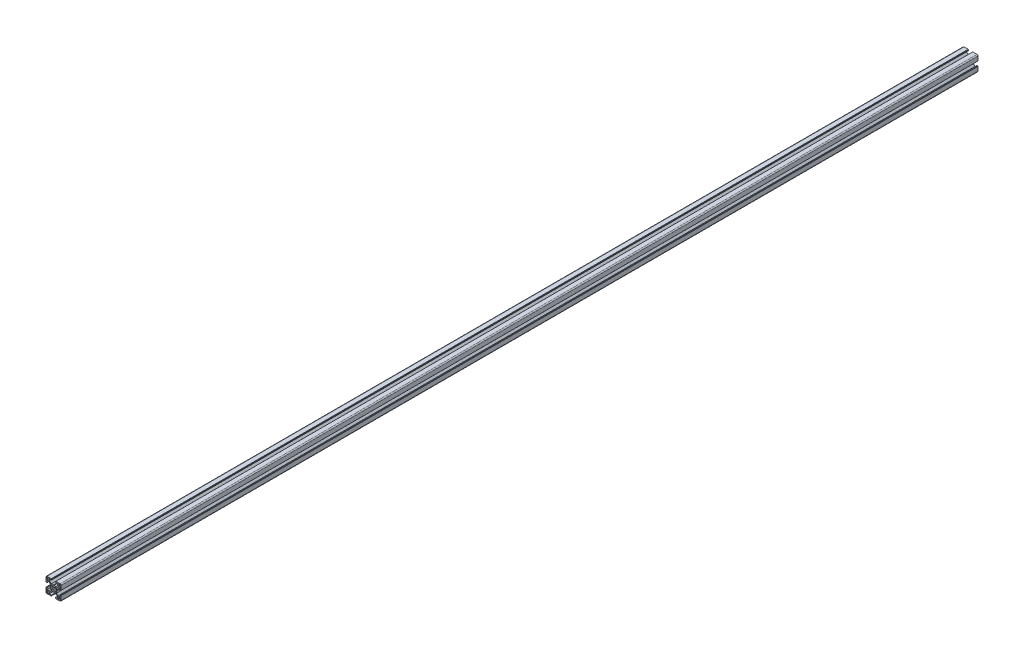
SolidWorks part; units mm, degrees
material "6061-T6 (SS)"
ref_plane "Front Plane" through (0, 0, 0) normal (0, 0, 1) x (1, 0, 0)
ref_plane "Top Plane" through (0, 0, 0) normal (0, 1, 0) x (1, 0, 0)
ref_plane "Right Plane" through (0, 0, 0) normal (1, 0, 0) x (0, 0, -1)
sketch "Sketch2" plane through (0, 0, 0) normal (0, 0, 1) x (1, 0, 0)
  line L0 (0, 15) -> (0, -15) construction
  line L1 (-15, 0) -> (15, 0) construction
  line L2 (4, -15) -> (15, -15)
  line L3 (15, -15) -> (15, -4)
  line L4 (4, -15) -> (4, -12.885)
  line L6 (8.25, -9.7455) -> (4.5045, -6)
  line L7 (0, 0) -> (15, -15) construction
  line L8 (15, -4) -> (12.885, -4)
  line L11 (4.55, -15) -> (4.55, -14.45) construction
  line L12 (4, -12.885) -> (8.25, -12.885)
  line L13 (8.25, -12.885) -> (8.25, -9.7455)
  line L14 (4.55, -14.45) -> (4, -14.45) construction
  line L15 (14.45, -4) -> (14.45, -4.55) construction
  line L16 (14.45, -4.55) -> (15, -4.55) construction
  line L17 (12.885, -4) -> (12.885, -8.25)
  line L18 (12.885, -8.25) -> (9.7455, -8.25)
  line L19 (9.7455, -8.25) -> (6, -4.5045)
  line L20 (7.8728, -6.3772) -> (6.3772, -7.8728) construction
  line L21 (11.625, -13.875) -> (11.625, -15) construction
  line L22 (9.375, -13.875) -> (13.875, -13.875)
  line L23 (9.375, -13.875) -> (9.375, -9.375)
  line L24 (9.375, -9.375) -> (13.875, -9.375)
  line L25 (13.875, -13.875) -> (13.875, -9.375)
  line L26 (11.625, -9.375) -> (11.625, -13.875) construction
  line L27 (9.375, -11.625) -> (13.875, -11.625) construction
  line L28 (13.875, -11.625) -> (15, -11.625) construction
  line L29 (8.25, -12.885) -> (9.375, -12.885) construction
  line L30 (4.5045, -6) -> (0.6555, -6)
  line L31 (0.6555, -6) -> (0, -5.45)
  line L32 (0, -6) -> (0, -5.45) construction
  circle A0 centre (0, 0) radius 3.5
  arc A2 (9.375, -12.885) -> (10.365, -13.875) centre (10.365, -12.885) ccw construction
  point P8 (0, -6)
  point P15 (4.55, -15)
  point P16 (7.125, -7.125)
  point P33 (11.625, -11.625)
  dimension "Center Hole Diameter" = 7
  dimension "Rail Height" = 30
  dimension "Rail Width" = 30
  dimension "T-Slot Width" = 8
  dimension "Slot Depth" = 9
  dimension "Slot Inner Width" = 16.5
  dimension "Step Width" = 9.1
  dimension "D1" = 1.125
  dimension "D2" = 2.115
  dimension "D3" = 50
sketch "Sketch3" plane through (0, 0, 0) normal (1, 0, 0) x (0, 0, -1)
  line L0 (-76.2, -15) -> (76.2, -15) construction
  line L1 (-50.8, 0) -> (50.8, 0) construction
  dimension "D1" = 25.4
  dimension "Length" = 152.4
sketch "Sketch4" plane through (0, 0, 0) normal (0, 0, 1) x (1, 0, 0)
  line L22 (0, -5.45) -> (0.6555, -6)
  line L23 (0.6555, -6) -> (4.5045, -6)
  line L24 (4.5045, -6) -> (8.25, -9.7455)
  line L25 (8.25, -9.7455) -> (8.25, -12.885)
  line L26 (8.25, -12.885) -> (4, -12.885)
  line L27 (4, -12.885) -> (4, -14.45)
  line L28 (4, -14.45) -> (4.55, -14.45)
  line L29 (4.55, -14.45) -> (4.55, -15)
  line L30 (4.55, -15) -> (12.885, -15)
  line L31 (4, -15) -> (15, -15) construction
  line L32 (15, -15) -> (15, -4) construction
  line L33 (15, -12.885) -> (15, -4.55)
  line L34 (15, -4.55) -> (14.45, -4.55)
  line L35 (14.45, -4.55) -> (14.45, -4)
  line L36 (14.45, -4) -> (12.885, -4)
  line L37 (12.885, -4) -> (12.885, -8.25)
  line L38 (12.885, -8.25) -> (9.7455, -8.25)
  line L39 (9.7455, -8.25) -> (6, -4.5045)
  line L40 (6, -4.5045) -> (6, -0.6555)
  line L41 (6, -0.6555) -> (5.45, 0)
  line L42 (-15, 0) -> (15, 0) construction
  line L43 (0, -5.45) -> (0, -3.5)
  line L44 (0, 15) -> (0, -15) construction
  line L45 (3.5, 0) -> (5.45, 0)
  line L46 (1.8108, -2.9952) -> (3.4913, -4.6757)
  line L47 (3.4913, -4.6757) -> (4.6757, -3.4913)
  line L48 (4.6757, -3.4913) -> (2.9952, -1.8108)
  line L49 (0, 0) -> (15, -15) construction
  line L50 (9.375, -13.875) -> (13.875, -13.875) construction
  line L51 (13.875, -13.875) -> (13.875, -9.375) construction
  line L52 (9.375, -13.875) -> (9.375, -9.375) construction
  line L53 (9.375, -9.375) -> (13.875, -9.375) construction
  line L54 (9.375, -10.365) -> (9.375, -12.885)
  line L55 (10.365, -13.875) -> (12.885, -13.875)
  line L56 (13.875, -12.885) -> (13.875, -10.365)
  line L57 (10.365, -9.375) -> (12.885, -9.375)
  arc A12 (12.885, -15) -> (15, -12.885) centre (12.885, -12.885) ccw
  circle A13 centre (0, 0) radius 3.5 construction
  arc A14 (0, -3.5) -> (1.8108, -2.9952) centre (0, 0) ccw
  arc A15 (3.5, 0) -> (2.9952, -1.8108) centre (0, 0) cw
  circle A16 centre (0, 0) radius 5.775 construction
  arc A17 (9.375, -12.885) -> (10.365, -13.875) centre (10.365, -12.885) ccw
  arc A18 (9.375, -12.885) -> (10.365, -13.875) centre (10.365, -12.885) ccw construction
  arc A19 (12.885, -13.875) -> (13.875, -12.885) centre (12.885, -12.885) ccw
  arc A20 (9.375, -10.365) -> (10.365, -9.375) centre (10.365, -10.365) cw
  arc A21 (12.885, -9.375) -> (13.875, -10.365) centre (12.885, -10.365) cw
  point P40 (4.0835, -4.0835)
  dimension "D1" = 11.55
  dimension "D2" = 0.22
extrude "Boss-Extrude1" add sketch "Sketch4" along normal blind 1828.8
mirror "Mirror1" about plane through (0, 0, 0) normal (1, 0, 0) of bodies 134
mirror "Mirror2" about plane through (0, 0, 0) normal (0, 1, 0) of bodies 135
sketch "Sketch5" plane through (0, 0, 1828.8) normal (0, 0, 1) x (1, 0, 0)
  line L0 (-5.675, 12.885) -> (-5.4, 13.16)
  line L1 (-8.25, 12.885) -> (-4, 12.885) construction
  line L2 (-5.4, 13.16) -> (-5.125, 12.885)
  line L3 (0, 15) -> (0, -15) construction
  line L4 (-5.675, 12.885) -> (-5.125, 12.885)
  dimension "D1" = 0.275
  dimension "D2" = 5.4
extrude "Cut-Extrude1" cut sketch "Sketch5" against normal through all both and the other way through all
equation "\"D1@Boss-Extrude1\"= \"table_length\""
equation "\"D1@Sketch2\"=\"Slot Depth@Sketch2\"*0.125"
equation "\"D2@Sketch2\"=\"Slot Depth@Sketch2\"*0.235"
equation "\"D1@Sketch4\"=\"Center Hole Diameter@Sketch2\"*1.65"
equation "\"D2@Sketch4\"=(\"Step Width@Sketch2\"-\"T-Slot Width@Sketch2\")*0.2"
equation "\"D1@Sketch5\"=(\"Step Width@Sketch2\"-\"T-Slot Width@Sketch2\")*0.5*0.5"
equation "\"D2@Sketch5\"=\"T-Slot Width@Sketch2\"*1.35*0.5"
equation "\"altitude_horizontal_rail_length\"=10in"
equation "\"altitude_vertictal_rail_length\"=12in"
equation "\"table_length\"=72in"
equation "\"table_width\"=25in"
equation "\"table_thickness\"=1.75in"
